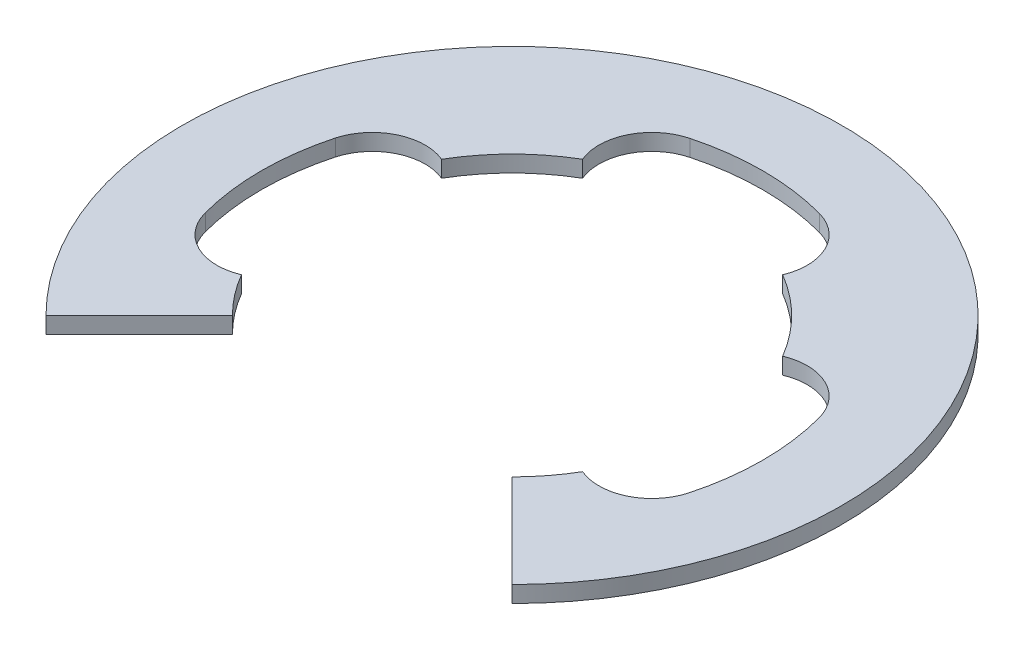
SolidWorks part; units mm, degrees
ref_plane "Front Plane" through (0, 0, 0) normal (0, 0, 1) x (1, 0, 0)
ref_plane "Top Plane" through (0, 0, 0) normal (0, 1, 0) x (1, 0, 0)
ref_plane "Right Plane" through (0, 0, 0) normal (1, 0, 0) x (0, 0, -1)
sketch "Sketch2" plane through (0, 0, 0) normal (0, 1, 0) x (1, 0, 0)
  circle A0 centre (0, 0) radius 15.875
  dimension "D1" = 31.75
extrude "Boss-Extrude1" add sketch "Sketch2" along normal blind 0.7937
sketch "Sketch3" plane through (0, 0.7937, 0) normal (0, 1, 0) x (1, 0, 0)
  circle A0 centre (0, 0) radius 9.525
extrude "Cut-Extrude1" cut sketch "Sketch3" against normal through all
sketch "Sketch4" plane through (0, 0, 0) normal (1, 0, 0) x (0, 0, -1)
  line L1 (0, -0.92) -> (-22.3182, -0.92)
  line L2 (0, -0.92) -> (0, 7.4371)
  line L3 (0, 7.4371) -> (-22.3182, 7.4371)
  line L4 (-22.3182, -0.92) -> (-22.3182, 7.4371)
revolve "Cut-Revolve1" cut sketch "Sketch4" angle 45 about L2 other way angle 45
sketch "Sketch5" plane through (0, 0.7937, 0) normal (0, 1, 0) x (1, 0, 0)
  arc A2 (6.7351, 1.8047) -> (6.7351, -1.8047) centre (0, 0) cw
  arc A3 (11.6729, 3.0987) -> (11.6584, -3.1529) centre (0, 0) cw
  arc A4 (11.6584, -3.1529) -> (6.7351, -1.8047) centre (9.2004, -2.4653) cw
  arc A5 (11.6729, 3.0987) -> (6.7351, 1.8047) centre (9.2004, 2.4653) ccw
  point P2 (6.7351, 1.8047)
  point P3 (6.7351, -1.8047)
  point P4 (11.6646, -3.1302)
  point P10 (11.6729, 3.0987)
extrude "Cut-Extrude2" cut sketch "Sketch5" against normal through all
pattern_circular "CirPattern1" count 4 over 360 about axis through (0, 0, 0) along (0, 1, 0) of "Cut-Extrude2"
